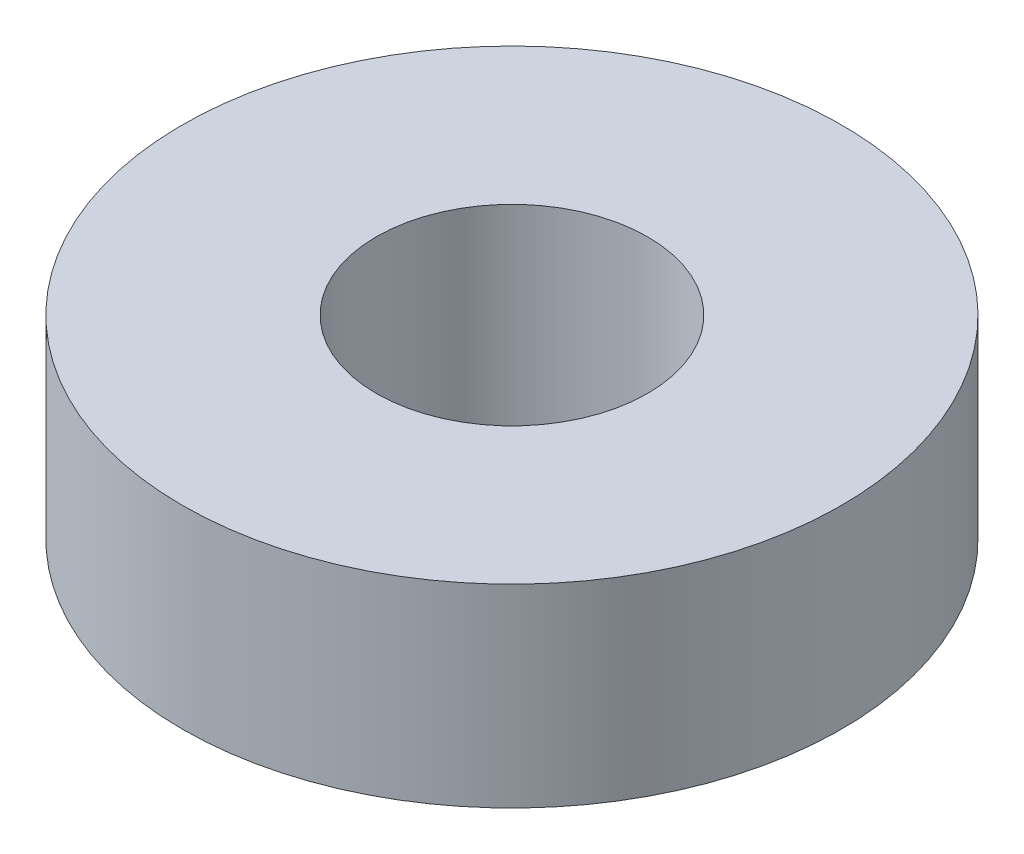
SolidWorks part; units mm, degrees
ref_plane "Front Plane" through (0, 0, 0) normal (0, 0, 1) x (1, 0, 0)
ref_plane "Top Plane" through (0, 0, 0) normal (0, 1, 0) x (1, 0, 0)
ref_plane "Right Plane" through (0, 0, 0) normal (1, 0, 0) x (0, 0, -1)
sketch "Sketch1" plane through (0, 0, 0) normal (0, 1, 0) x (1, 0, 0)
  circle A0 centre (0, 0) radius 42.5
  dimension "FLANGE_OD" = 85
extrude "Boss-Extrude1" add sketch "Sketch1" along normal blind 25
sketch "Sketch2" plane through (0, 0, 0) normal (0, 1, 0) x (1, 0, 0)
  circle A0 centre (0, 0) radius 17.5
  dimension "BORE_D" = 35
extrude "Cut-Extrude1" cut sketch "Sketch2" along normal through all
sketch "Sketch3" plane through (0, 25, 0) normal (0, 1, 0) x (1, 0, 0)
  circle A0 centre (0, 0) radius 12.8997 construction
  circle A1 centre (-12.8997, 0) radius 3.6078
  dimension "BOLT_D" = 7.2156
  dimension "BOLT_PCD" = 25.7994
extrude "Cut-Extrude2" cut sketch "Sketch3" against normal blind 24.2862 rebuild error yes
pattern_circular "CirPattern1" count 5 over 360 rebuild error yes
